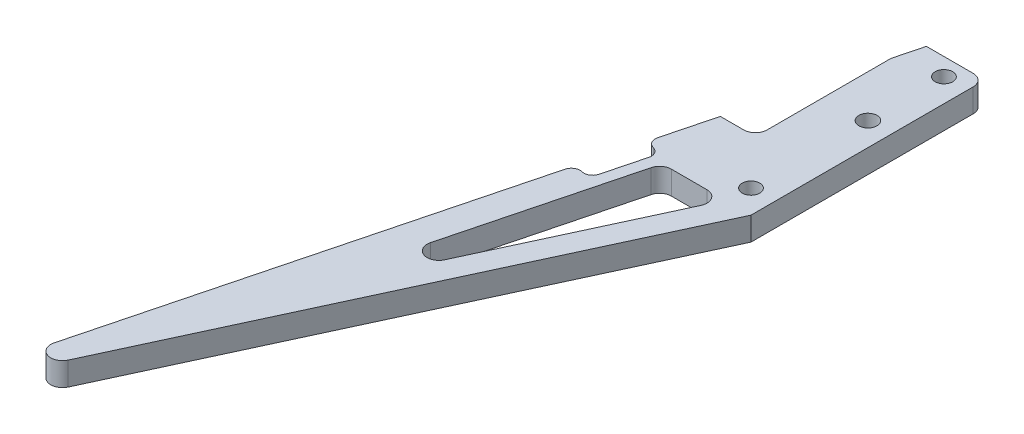
SolidWorks part; units mm, degrees
material "Thornel Mat VMA"
ref_plane "前视基准面" through (0, 0, 0) normal (0, 0, 1) x (1, 0, 0)
ref_plane "上视基准面" through (0, 0, 0) normal (0, 1, 0) x (1, 0, 0)
ref_plane "右视基准面" through (0, 0, 0) normal (1, 0, 0) x (0, 0, -1)
sketch "Sketch1" plane through (0, 0, 0) normal (0, 1, 0) x (1, 0, 0)
  line L1 (-5, 20) -> (5, 20)
  line L2 (-5, 20) -> (-5, -20)
  line L3 (-5, -20) -> (5, -20)
  line L4 (5, 20) -> (5, -20)
  line L5 (-5, 20) -> (5, -20) construction
  line L6 (-5, -20) -> (5, 20) construction
  point P0 (0, 0)
  dimension "D1" = 10
  dimension "D2" = 40
extrude "Boss-Extrude1" add sketch "Sketch1" along normal blind 4
sketch "Sketch3" plane through (0, 0, 0) normal (0, -1, 0) x (1, 0, 0)
  circle A0 centre (1, 16) radius 1.5
  circle A1 centre (1, -4) radius 1.55
  circle A2 centre (1, -17) radius 1.5
extrude "Cut-Extrude1" cut sketch "Sketch3" against normal blind 4
ref_plane "Plane1" through (-5, 0, 20) normal (0, 0, 1) x (1, 0, 0)
sketch "Sketch7" plane through (0, 4, 0) normal (0, 1, 0) x (1, 0, 0)
  line L0 (-5, 20) -> (-41.2309, -120)
  line L1 (5, 20) -> (-5, 20) construction
  line L2 (-5, 20) -> (-5, -20) construction
  line L3 (-41.2309, -120) -> (5, -20)
  line L4 (5, -20) -> (-5, -20)
  line L5 (-5, -20) -> (5, -20) construction
  line L6 (-5, -20) -> (-5, 20)
  dimension "D1" = 100
extrude "Boss-Extrude5" add sketch "Sketch7" against normal blind 4
sketch "Sketch8" plane through (0, 4, 0) normal (0, 1, 0) x (1, 0, 0)
  line L0 (-10.187, -20) -> (-23.8951, -72.9695)
  line L1 (-23.8951, -72.9695) -> (0.5932, -20)
  line L2 (0.5932, -20) -> (-10.187, -20)
  line L3 (-41.2309, -120) -> (5, -20) construction
  line L4 (-5, 20) -> (-41.2309, -120) construction
  line L5 (5, 20) -> (-5, 20) construction
  dimension "D1" = 4
  dimension "D2" = 5
  dimension "D3" = 40
extrude "Cut-Extrude2" cut sketch "Sketch8" against normal blind 4
fillet "Fillet1" radius 2 5 edges at (-41.2309, 2, 120) (-10.187, 2, 20) (0.5932, 2, 20) (-23.8951, 2, 72.9695) (5, 2, -20)
sketch "Sketch9" plane through (0, 4, 0) normal (0, 1, 0) x (1, 0, 0)
  line L0 (-6.2462, 15.1846) -> (-6.2462, -8)
  line L1 (-5, 20) -> (-35.6724, -98.5214) construction
  line L2 (-6.2462, -8) -> (-12.2462, -8)
  line L3 (-12.2462, -8) -> (-6.2462, 15.1846)
  line L4 (-60, -20) -> (50, -20) construction
  dimension "D1" = 6
  dimension "D2" = 12
extrude "Cut-Extrude3" cut sketch "Sketch9" against normal blind 10
fillet "Fillet2" radius 2 1 edges at (-6.2462, 2, 8)
sketch "Sketch10" plane through (0, 4, 0) normal (0, 1, 0) x (1, 0, 0)
  line L0 (-14.8261, -17.969) -> (-11.9218, -18.7206)
  line L1 (-12.2462, -8) -> (-35.6724, -98.5214) construction
  line L2 (-11.9218, -18.7206) -> (-14.4271, -28.4017)
  line L3 (-14.4271, -28.4017) -> (-17.3315, -27.6501)
  line L4 (-17.3315, -27.6501) -> (-14.8261, -17.969)
  dimension "D1" = 3
  dimension "D2" = 10
extrude "Cut-Extrude4" cut sketch "Sketch10" against normal blind 10
fillet "Fillet3" radius 1.5 4 edges at (-14.4271, 2, 28.4017) (-17.3315, 2, 27.6501) (-11.9218, 2, 18.7206) (-14.8261, 2, 17.969)
